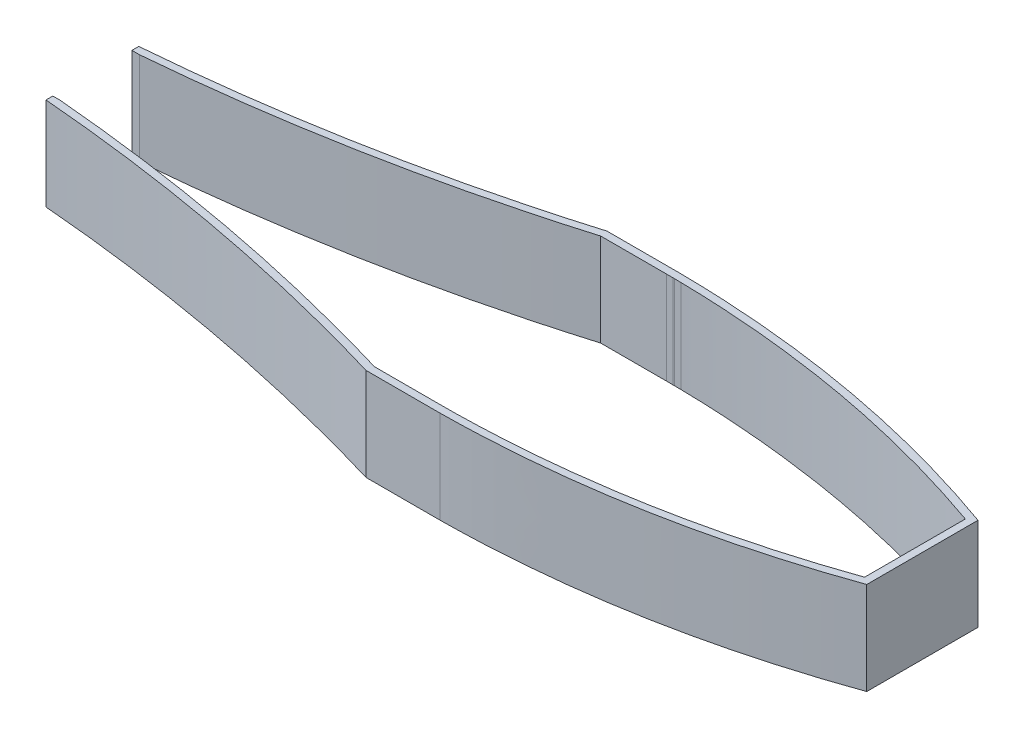
SolidWorks part; units mm, degrees
material "Nylon 101"
ref_plane "Front Plane" through (0, 0, 0) normal (0, 0, 1) x (1, 0, 0)
ref_plane "Top Plane" through (0, 0, 0) normal (0, 1, 0) x (1, 0, 0)
ref_plane "Right Plane" through (0, 0, 0) normal (1, 0, 0) x (0, 0, -1)
sketch "Sketch1" plane through (0, 0, 0) normal (0, 1, 0) x (1, 0, 0)
  line L0 (0, 0) -> (0, 32.5)
  line L1 (0, 0) -> (97.5, 0)
  line L2 (97.5, 0) -> (97.5, 15)
  line L3 (48.75, 0) -> (0, 32.5)
  line L4 (24.375, 16.25) -> (24.375, 31.25)
  line L5 (2, 2) -> (2, 30.4722)
  line L6 (2, 2) -> (95.5, 2)
  line L7 (95.5, 2) -> (95.5, 13.5863)
  spline S0 degree 2 poles (97.5, 15) (49.8673, 31.9791) (0, 32.5) knots 0 0 0 1 1 1
  spline S1 degree 1 poles (95.5, 13.5863) (2, 30.4722) knots 0 0 1 1 construction
  spline S2 degree 3 poles (95.5, 13.5863) (91.704, 14.9201) (84.04, 17.4467) (68.6812, 21.8453) (49.3064, 26.1584) (29.7203, 28.8815) (13.9286, 30.1079) (5.9734, 30.4039) (2, 30.4722) knots 0.01403 0.01403 0.01403 0.01403 0.134725 0.25542 0.496811 0.738202 0.858897 0.979593 0.979593 0.979593 0.979593
  point P3 (48.75, 0)
  dimension "D1" = 32.5
  dimension "D2" = 97.5
  dimension "D3" = 15
  dimension "D4" = 15
  dimension "D5" = 2
extrude "Boss-Extrude1" add sketch "Sketch1" against normal blind 12.5 and the other way blind 12.5 contours L1 L3 L0 | L2 S0 L4 L3 L1 | L4 S0 L3 region at (0.5859, 0, -16.25) region at (12.9441, 0, -31.0322) region at (47.6911, 0, -1.6617)
sketch "Sketch2" plane through (0, 12.5, 0) normal (0, 1, 0) x (1, 0, 0)
  line L0 (0, 32.5) -> (0, 29)
  line L1 (0, 0) -> (0, 32.5) construction
  line L2 (97.5, 0) -> (94, 0)
  line L3 (0, 0) -> (97.5, 0) construction
  circle A0 centre (0, 29) radius 1.5
  circle A1 centre (94, 0) radius 1.5
  dimension "D2" = 3
  dimension "D4" = 3
  dimension "D1" = 3.5
  dimension "D3" = 3.5
extrude "Cut-Extrude1" cut sketch "Sketch2" against normal through all contours A0 | A1
sketch "Sketch3" plane through (0, 0, 0) normal (0, 1, 0) x (1, 0, 0)
  line L0 (0, 0) -> (-46.25, 0)
  line L1 (-46.25, 0) -> (-56.25, 0)
  line L2 (-56.25, 0) -> (-86.25, 0)
  line L3 (-86.25, 0) -> (-116.25, 0)
  line L4 (-116.25, 0) -> (-126.25, 0)
  line L5 (0, 32.5) -> (-20, 32.5)
  line L6 (-126.25, 0) -> (-126.25, 12.5)
  line L7 (-71.25, 0) -> (-71.25, 20)
  line L8 (0, 32.5) -> (0, 29)
  line L9 (0, 27.5) -> (0, 0)
  line L10 (-2, 27.5) -> (-2, 2)
  line L11 (-2, 2) -> (-46.25, 2)
  line L12 (-46.25, 2) -> (-56.25, 2)
  line L13 (-56.25, 2) -> (-86.25, 2)
  line L14 (-86.25, 2) -> (-116.25, 2)
  line L15 (-116.25, 2) -> (-124.25, 2)
  line L16 (-124.25, 2) -> (-124.25, 10.662)
  line L17 (-2, 30.5) -> (-19.7087, 30.5)
  line L18 (-2, 30.5) -> (-2, 29)
  line L19 (-2, 27.5) -> (-2, 29)
  circle A0 centre (-116.25, 0) radius 1.5
  circle A1 centre (-86.25, 0) radius 1.5
  circle A2 centre (-56.25, 0) radius 1.5
  circle A3 centre (0, 29) radius 1.5
  spline S0 degree 2 poles (-126.25, 12.5) (-72.0797, 16.9872) (-20, 32.5) knots 0 0 0 1 1 1
  spline S1 degree 1 poles (-124.25, 10.662) (-19.7087, 30.5) knots 0 0 1 1 construction
  spline S2 degree 3 poles (-124.25, 10.662) (-115.3902, 11.4269) (-97.6865, 13.4055) (-71.4331, 17.7001) (-45.4314, 23.3216) (-28.2331, 27.966) (-19.7087, 30.5) knots 0.016878 0.016878 0.016878 0.016878 0.26199 0.507102 0.752213 0.997325 0.997325 0.997325 0.997325
  dimension "D6" = 3
  dimension "D7" = 3
  dimension "D8" = 3
  dimension "D12" = 3
  dimension "D1" = 46.25
  dimension "D2" = 10
  dimension "D3" = 30
  dimension "D4" = 30
  dimension "D5" = 10
  dimension "D9" = 20
  dimension "D10" = 12.5
  dimension "D11" = 20
  dimension "D13" = 2
extrude "Boss-Extrude2" add sketch "Sketch3" along normal blind 12.5 and the other way blind 12.5 contours L16 S2 L7 S0 L6 L4 A0 L3 A1 L2 L13 L14 L15 | L7 S2 L17 L18 L19 L10 L11 L12 L13 L2 A2 L1 L0 L9 A3 L8 L5 S0 region at (-23.125, 0, -0.7831) region at (-78, 0, -0.5852)
mirror "Mirror1" about plane through (0, 0, 0) normal (0, 0, 1) of "Boss-Extrude2", "Boss-Extrude1"
sketch "Sketch5" plane through (0, 12.5, 0) normal (0, 1, 0) x (1, 0, 0)
  line L0 (-124.25, 2) -> (-124.25, -2)
  line L1 (-124.25, -2) -> (95.5, -2)
  line L2 (95.5, -2) -> (95.5, 2)
  line L3 (95.5, 2) -> (-124.25, 2)
extrude "Cut-Extrude4" cut sketch "Sketch5" against normal through all
sketch "Sketch6" plane through (0, 12.5, 0) normal (0, 1, 0) x (1, 0, 0)
  line L0 (-2, 2) -> (2, 2)
  line L1 (2, 2) -> (2, 30.4722)
  line L2 (2, 30.4722) -> (-2, 30.5)
  line L3 (-2, 30.5) -> (-2, 2)
extrude "Cut-Extrude5" cut sketch "Sketch6" against normal through all
mirror "Mirror2" about plane through (0, 0, 0) normal (0, 0, 1) of "Cut-Extrude5"
sketch "Sketch7" plane through (0, 12.5, 0) normal (0, 1, 0) x (1, 0, 0)
  line L0 (-124.25, 10.662) -> (-124.25, -10.662)
  line L1 (-124.25, -10.662) -> (-126.25, -10.662)
  line L2 (-126.25, -12.5) -> (-126.25, 12.5) construction
  line L3 (-126.25, -10.662) -> (-126.25, 10.662)
  line L4 (-126.25, 10.662) -> (-124.25, 10.662)
extrude "Cut-Extrude6" cut sketch "Sketch7" against normal through all
